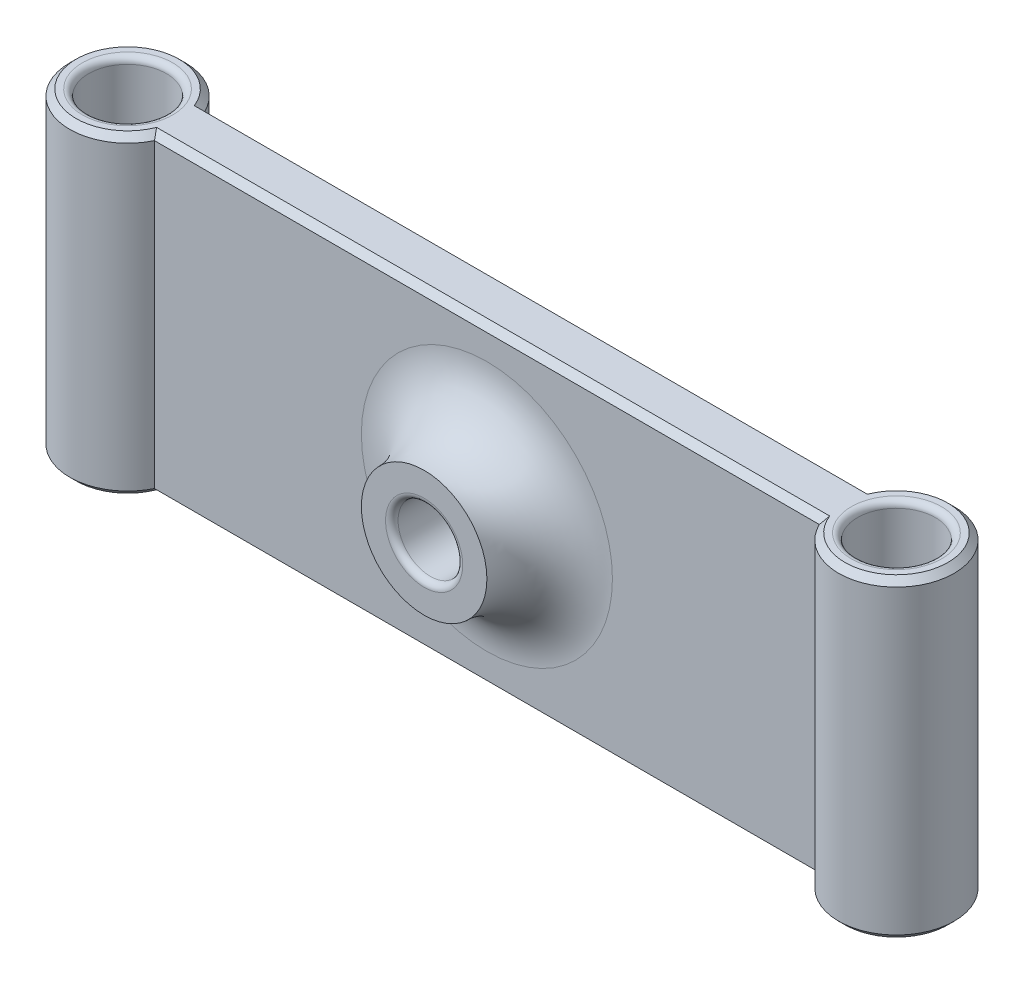
SolidWorks part; units mm, degrees
ref_plane "Front Plane" through (0, 0, 0) normal (0, 0, 1) x (1, 0, 0)
ref_plane "Top Plane" through (0, 0, 0) normal (0, 1, 0) x (1, 0, 0)
ref_plane "Right Plane" through (0, 0, 0) normal (1, 0, 0) x (0, 0, -1)
sketch "Sketch1" plane through (0, 0, 0) normal (0, 1, 0) x (1, 0, 0)
  line L0 (-50.4787, 0) -> (58.9286, 0) construction
  line L1 (0, 47.907) -> (0, -37.7672) construction
  line L2 (-52.9651, 4) -> (52.9651, 4)
  line L3 (-52.9651, -4) -> (52.9651, -4)
  circle A0 centre (-61.25, 0) radius 6.2
  arc A1 (-52.9651, 4) -> (-52.9651, -4) centre (-61.25, 0) ccw
  arc A2 (52.9651, 4) -> (52.9651, -4) centre (61.25, 0) cw
  circle A3 centre (61.25, 0) radius 6.2
  dimension "D1" = 12.4
  dimension "D2" = 3
  dimension "D3" = 122.5
  dimension "D4" = 8
extrude "Boss-Extrude1" add sketch "Sketch1" along normal blind 50
sketch "Sketch2" plane through (0, 0, 4) normal (0, 0, 1) x (1, 0, 0)
  line L0 (0, 54.7357) -> (0, -19.4241) construction
  line L1 (-52.9651, 0) -> (52.9651, 0) construction
  circle A0 centre (0, 25) radius 5.15
  circle A1 centre (0, 25) radius 10
  dimension "D1" = 10.3
  dimension "D3" = 20
  dimension "D2" = 25
extrude "Boss-Extrude2" add sketch "Sketch2" along normal blind 10 and the other way blind 15
sketch "Sketch3" plane through (0, 0, 4) normal (0, 0, 1) x (1, 0, 0)
  circle A2 centre (0, 25) radius 5.15
  circle A3 centre (0, 25) radius 5.15
  dimension "D1" = 0
extrude "Cut-Extrude2" cut sketch "Sketch3" against normal blind 10
fillet "Fillet1" radius 10 2 edges at (10, 25, -4) (-10, 25, 4)
fillet "Fillet2" radius 1 6 edges at (-61.25, 0, 6.2) (61.25, 0, -6.2) (61.25, 50, -6.2) (-61.25, 50, 6.2) (5.15, 25, -11) (5.15, 25, 14)
chamfer "Chamfer1" distance 1 angle 45 8 edges at (0, 50, -4) (70.45, 50, 0) (0, 50, 4) (-70.45, 50, 0) (0, 0, 4) (70.45, 0, 0) (0, 0, -4) (-70.45, 0, 0)
